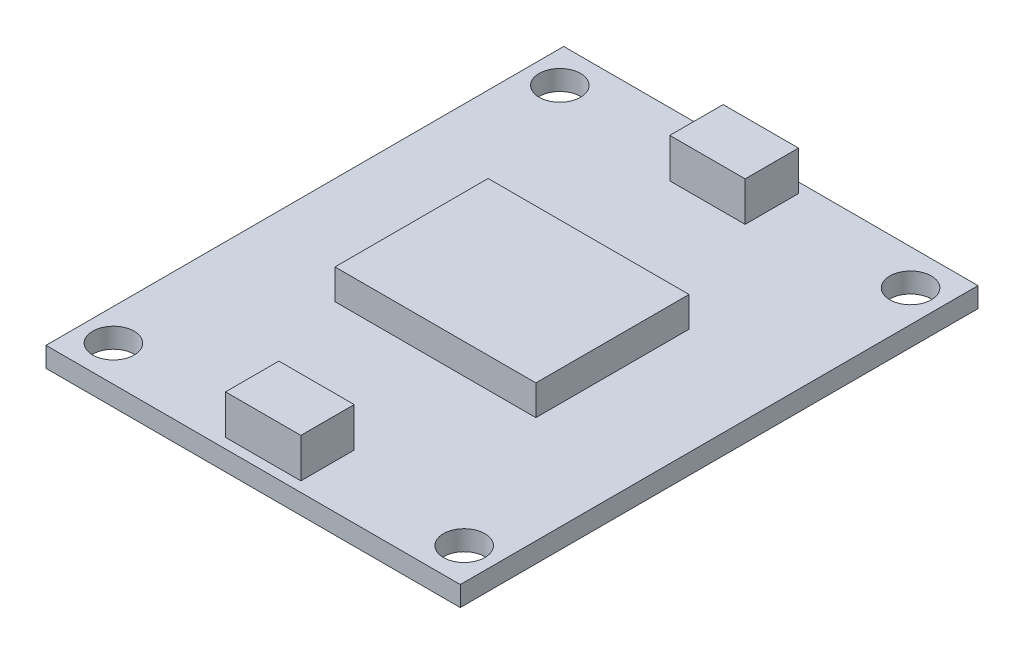
SolidWorks part; units mm, degrees
other "Markup1"
sketch "Sketch5" plane through (-16.5, 1.59, 20.62) normal (-0.0427, 0.7711, 0.6353) x (0.9965, 0.0785, -0.0282)
ref_plane "Front Plane" through (0, 0, 0) normal (0, 0, 1) x (1, 0, 0)
ref_plane "Top Plane" through (0, 0, 0) normal (0, 1, 0) x (1, 0, 0)
ref_plane "Right Plane" through (0, 0, 0) normal (1, 0, 0) x (0, 0, -1)
sketch "Sketch1" plane through (0, 0, 0) normal (0, 1, 0) x (1, 0, 0)
  line L0 (13.97, 17.78) -> (-13.97, -17.78) construction
  line L1 (-16.5, -20.62) -> (16.5, -20.62)
  line L2 (-16.5, -20.62) -> (-16.5, 20.62)
  line L3 (-16.5, 20.62) -> (16.5, 20.62)
  line L4 (16.5, -20.62) -> (16.5, 20.62)
  line L5 (-16.5, -20.62) -> (16.5, 20.62) construction
  line L6 (-16.5, 20.62) -> (16.5, -20.62) construction
  line L7 (-13.97, -17.78) -> (13.97, -17.78) construction
  line L8 (-13.97, -17.78) -> (-13.97, 17.78) construction
  line L9 (-13.97, 17.78) -> (13.97, 17.78) construction
  line L10 (13.97, -17.78) -> (13.97, 17.78) construction
  line L11 (-13.97, 17.78) -> (13.97, -17.78) construction
  circle A0 centre (0, 0) radius 26.409 construction
  point P0 (0, 0)
  point P6 (0, 0)
  point P10 (0, 0)
  dimension "D5" = 52.818
  dimension "D1" = 33
  dimension "D2" = 41.24
  dimension "D3" = 27.94
  dimension "D4" = 35.56
extrude "Boss-Extrude1" add sketch "Sketch1" along normal blind 1.59 contours L2 L3 L4 L1
hole_wizard "M3 Clearance Hole1" positions "Sketch2" profile "Sketch4" hole size "M3" standard "ANSI Metric" end condition through all
sketch "Sketch2" plane through (0, 1.59, 0) normal (0, 1, 0) x (1, 0, 0)
  point P0 (-13.97, 17.78)
  point P3 (13.97, 17.78)
  point P6 (13.97, -17.78)
  point P9 (-13.97, -17.78)
sketch "Sketch4" plane through (-13.97, 1.59, -17.78) normal (1, 0, 0) x (0, 0, 1)
  line L0 (0, 0) -> (0, 1.59)
  line L1 (0, 1.59) -> (1.65, 1.59)
  line L2 (1.65, 1.59) -> (1.65, 0)
  line L5 (1.65, 0) -> (0, 0)
  line L11 (0, -6.35) -> (0, 107.95) construction
  dimension "Thru Hole Dia." = 3.3
  dimension "Thru Hole Depth" = 1.59
sketch "Sketch6" plane through (0, 1.59, 0) normal (0, 1, 0) x (1, 0, 0)
  line L1 (-8, 6.1) -> (8, 6.1)
  line L2 (-8, 6.1) -> (-8, -6.1)
  line L3 (-8, -6.1) -> (8, -6.1)
  line L4 (8, 6.1) -> (8, -6.1)
  line L5 (0, -6.1) -> (0, 6.1) construction
  line L6 (-8, 0) -> (8, 0) construction
  point P0 (0, 0)
  dimension "D1" = 16
  dimension "D2" = 12.2
extrude "M8P" add sketch "Sketch6" along normal blind 2.4
sketch "Sketch7" plane through (0, 1.59, 0) normal (0, 1, 0) x (1, 0, 0)
  line L0 (0, 0) -> (50000, 0) construction
  line L1 (0, 20.62) -> (0, -20.62) construction
  line L2 (-16.5, 20.62) -> (16.5, 20.62) construction
  line L3 (-16.5, -20.62) -> (16.5, -20.62) construction
  line L4 (-3, 17.695) -> (3, 17.695) construction
  line L5 (-3, -19.82) -> (3, -19.82)
  line L6 (-3, -19.82) -> (-3, -15.57)
  line L7 (-3, -15.57) -> (3, -15.57)
  line L8 (3, -19.82) -> (3, -15.57)
  line L9 (0, -15.57) -> (0, -19.82) construction
  line L10 (-3, -17.695) -> (3, -17.695) construction
  line L11 (0, 15.57) -> (0, 19.82) construction
  line L12 (3, 19.82) -> (3, 15.57)
  line L13 (-3, 15.57) -> (3, 15.57)
  line L14 (-3, 19.82) -> (-3, 15.57)
  line L15 (-3, 19.82) -> (3, 19.82)
  point P9 (0, -17.695)
  point P21 (0, 17.695)
  dimension "D1" = 6
  dimension "D2" = 4.25
  dimension "D3" = 0.8
extrude "I2C connectors" add sketch "Sketch7" along normal blind 3.14
ref_axis "Axis1" through (0, 4.9665, 0) along (0, -1, 0)
ref_plane "Plane1" through (0, 0, 0) normal (0.7863, 0, 0.6178) x (0.6178, 0, -0.7863)
